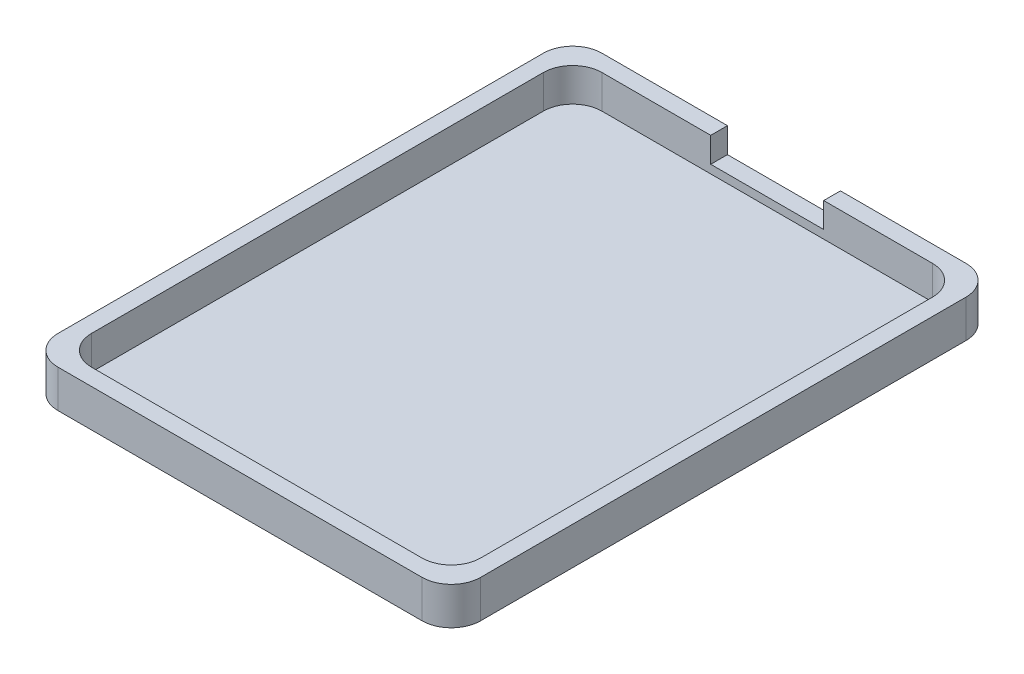
SolidWorks part; units mm, degrees
ref_plane "Alzado" through (0, 0, 0) normal (0, 0, 1) x (1, 0, 0)
ref_plane "Planta" through (0, 0, 0) normal (0, 1, 0) x (1, 0, 0)
ref_plane "Vista lateral" through (0, 0, 0) normal (1, 0, 0) x (0, 0, -1)
sketch "Sketch1" plane through (0, 0, 0) normal (0, 1, 0) x (1, 0, 0)
  line L1 (3.5, 0) -> (47, 0)
  line L2 (0, 3.5) -> (0, 61.5)
  line L3 (3.5, 65) -> (47, 65)
  line L4 (50.5, 3.5) -> (50.5, 61.5)
  arc A0 (47, 0) -> (50.5, 3.5) centre (47, 3.5) ccw
  arc A1 (3.5, 0) -> (0, 3.5) centre (3.5, 3.5) cw
  arc A2 (0, 61.5) -> (3.5, 65) centre (3.5, 61.5) cw
  arc A3 (47, 65) -> (50.5, 61.5) centre (47, 61.5) cw
  point P7 (50.5, 0)
  point P10 (0, 0)
  point P15 (50.5, 65)
  dimension "D3" = 3.5
  dimension "D1" = 50.5
  dimension "D2" = 65
extrude "Boss-Extrude1" add sketch "Sketch1" along normal blind 4.5
sketch "Sketch2" plane through (0, 4.5, 0) normal (0, 1, 0) x (1, 0, 0)
  line L0 (3.5, 0) -> (47, 0) construction
  line L1 (5.5, 2) -> (45, 2)
  line L2 (2, 5.5) -> (2, 59.5)
  line L3 (5.5, 63) -> (45, 63)
  line L4 (48.5, 5.5) -> (48.5, 59.5)
  line L5 (2, 2) -> (48.5, 63) construction
  line L6 (2, 63) -> (48.5, 2) construction
  line L7 (47, 65) -> (3.5, 65) construction
  line L8 (50.5, 3.5) -> (50.5, 61.5) construction
  line L9 (0, 61.5) -> (0, 3.5) construction
  arc A0 (5.5, 2) -> (2, 5.5) centre (5.5, 5.5) cw
  arc A1 (45, 2) -> (48.5, 5.5) centre (45, 5.5) ccw
  arc A2 (2, 59.5) -> (5.5, 63) centre (5.5, 59.5) cw
  arc A3 (45, 63) -> (48.5, 59.5) centre (45, 59.5) cw
  point P0 (25.25, 32.5)
  dimension "D5" = 3.5
  dimension "D1" = 2
  dimension "D2" = 2
  dimension "D3" = 2
  dimension "D4" = 2
extrude "Cut-Extrude1" cut sketch "Sketch2" against normal blind 4
sketch "Sketch3" plane through (0, 0, -65) normal (0, 0, -1) x (-1, 0, 0)
  line L0 (-47, 0) -> (-3.5, 0) construction
  line L6 (-32, 1.5) -> (-18.5, 1.5)
  line L7 (-32, 1.5) -> (-32, 7.5)
  line L8 (-32, 7.5) -> (-18.5, 7.5)
  line L9 (-18.5, 1.5) -> (-18.5, 7.5)
  line L10 (-25.25, 4.5) -> (-25.25, 0) construction
  line L11 (-47, 4.5) -> (-3.5, 4.5) construction
  line L12 (-32, 1.5) -> (-18.5, 7.5) construction
  line L13 (-32, 7.5) -> (-18.5, 1.5) construction
  dimension "D1" = 1.5
  dimension "D2" = 13.5
extrude "Cut-Extrude3" cut sketch "Sketch3" against normal blind 15
